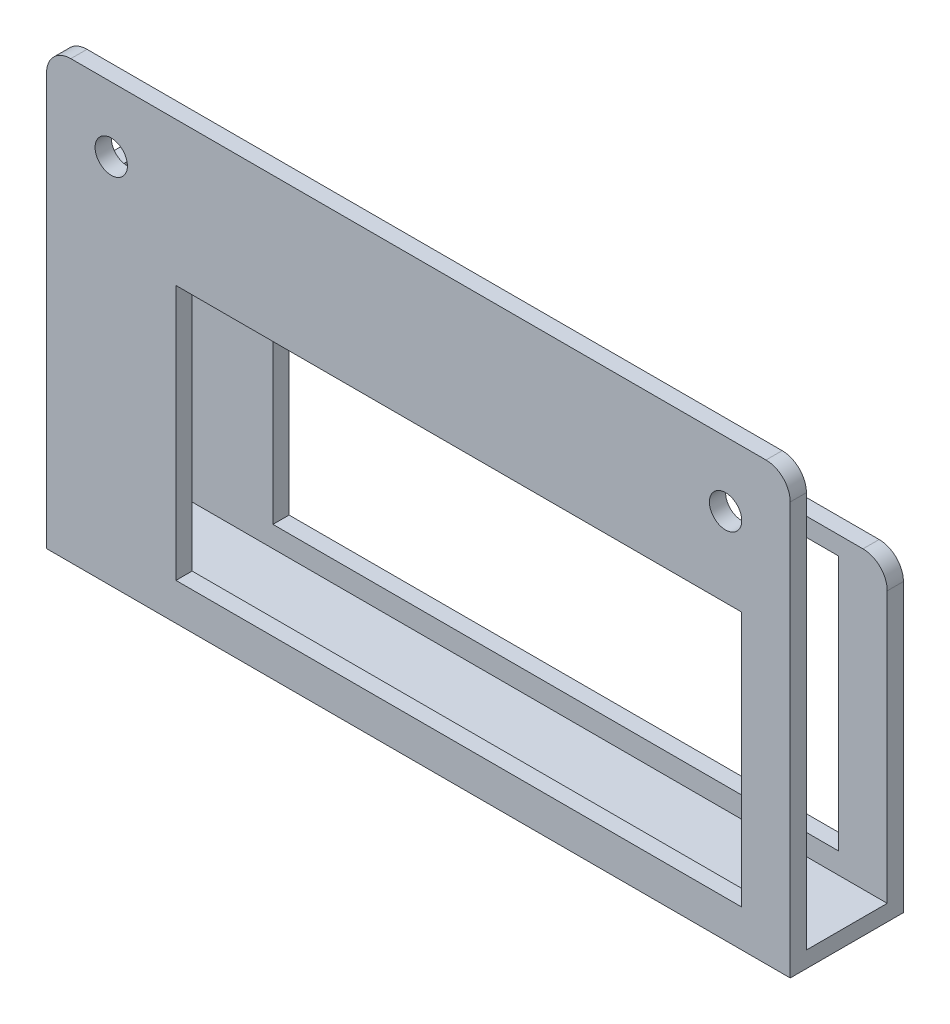
SolidWorks part; units mm, degrees
ref_plane "Alzado" through (0, 0, 0) normal (0, 0, 1) x (1, 0, 0)
ref_plane "Planta" through (0, 0, 0) normal (0, 1, 0) x (1, 0, 0)
ref_plane "Vista lateral" through (0, 0, 0) normal (1, 0, 0) x (0, 0, -1)
sketch "Croquis1" plane through (0, 0, 0) normal (0, 0, 1) x (1, 0, 0)
  line L1 (-92, 54) -> (0, 54)
  line L2 (-92, 54) -> (-92, 0)
  line L3 (-92, 0) -> (0, 0)
  line L4 (0, 54) -> (0, 0)
  line L5 (-92, 54) -> (0, 0) construction
  line L6 (-92, 0) -> (0, 54) construction
  line L7 (-76, 36.2) -> (-6, 36.2)
  line L8 (-76, 36.2) -> (-76, 4.6)
  line L9 (-76, 4.6) -> (-6, 4.6)
  line L10 (-6, 36.2) -> (-6, 4.6)
  line L11 (-76, 36.2) -> (-6, 4.6) construction
  line L12 (-76, 4.6) -> (-6, 36.2) construction
  circle A0 centre (-84, 46) radius 2
  circle A1 centre (-8, 46) radius 2
  point P0 (-46, 27)
  point P6 (-41, 20.4)
  dimension "D7" = 4
  dimension "D8" = 4
  dimension "D9" = 8
  dimension "D1" = 4.6
  dimension "D2" = 36.2
  dimension "D3" = 54
  dimension "D4" = 92
  dimension "D5" = 6
  dimension "D6" = 70
  dimension "D10" = 8
  dimension "D11" = 8
  dimension "D12" = 8
extrude "Saliente-Extruir1" add sketch "Croquis1" along normal blind 14
sketch "Croquis2" plane through (0, 0, 0) normal (1, 0, 0) x (0, 0, -1)
  line L0 (-2, 38.4797) -> (-2, 2)
  line L1 (-14, 54) -> (0, 54) construction
  line L2 (-2, 2) -> (-12, 2)
  line L3 (-12, 2) -> (-12, 36.9531)
  line L5 (-14, 0) -> (-14, 54) construction
  line L7 (-12, 54) -> (-2, 54)
  line L8 (0, 0) -> (0, 54) construction
  line L9 (-14, 0) -> (0, 0) construction
  line L10 (-12, 36.9531) -> (-12, 54)
  line L11 (-2, 38.4797) -> (0, 38.4797)
  line L12 (0, 38.4797) -> (0, 54)
  line L13 (-2, 54) -> (0, 54)
  dimension "D1" = 2
  dimension "D2" = 2
  dimension "D3" = 2
extrude "Cortar-Extruir1" cut sketch "Croquis2" against normal blind 90
sketch "Croquis3" plane through (0, 0, 0) normal (0, 0, -1) x (-1, 0, 0)
  line L1 (90, 38.4797) -> (92, 38.4797)
  line L2 (90, 38.4797) -> (90, 54)
  line L3 (90, 54) -> (92, 54)
  line L4 (92, 38.4797) -> (92, 54)
extrude "Cortar-Extruir2" cut sketch "Croquis3" against normal up to surface (12 mm away) up to face at (-41, 20.4, 12)
sketch "Croquis4" plane through (-92, 0, 0) normal (-1, 0, 0) x (0, 0, 1)
  line L0 (14, 54) -> (14, 0) construction
  line L1 (3, 2.3409) -> (11, 2.3409)
  line L2 (3, 2.3409) -> (3, 15.3409)
  line L3 (3, 15.3409) -> (11, 15.3409)
  line L4 (11, 2.3409) -> (11, 15.3409)
  line L5 (0, 38.4797) -> (0, 0) construction
  dimension "D1" = 13
  dimension "D2" = 3
  dimension "D3" = 3
extrude "Cortar-Extruir3" cut sketch "Croquis4" against normal up to surface (2 mm away) up to face at (-90, 20.2398, 7)
fillet "Redondeo1" radius 3 1 edges at (-92, 54, 13)
fillet "Redondeo2" radius 3 1 edges at (0, 54, 13)
fillet "Redondeo3" radius 3 1 edges at (0, 38.4797, 1)
sketch "Croquis5" plane through (0, 0, 0) normal (0, 0, -1) x (-1, 0, 0)
  line L1 (76, 36.2) -> (54, 36.2)
  line L2 (76, 36.2) -> (76, 37.7)
  line L3 (76, 37.7) -> (54, 37.7)
  line L4 (54, 36.2) -> (54, 37.7)
  dimension "D1" = 22
  dimension "D2" = 1.5
